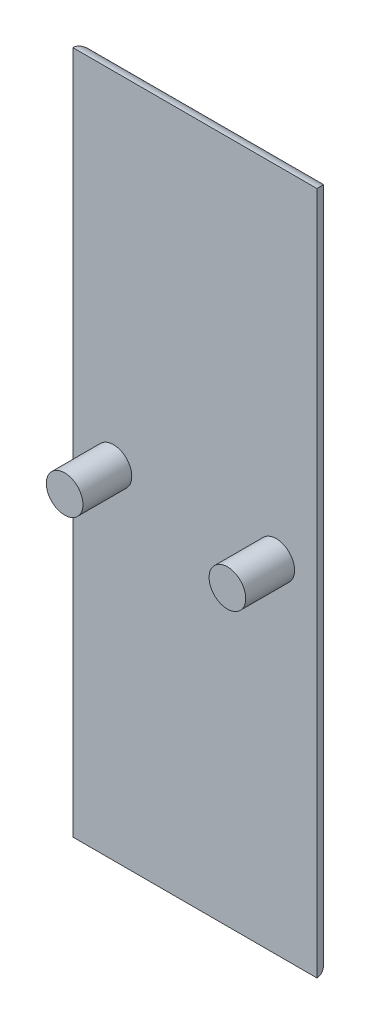
SolidWorks part; units mm, degrees
ref_plane "Front Plane" through (0, 0, 0) normal (0, 0, 1) x (1, 0, 0)
ref_plane "Top Plane" through (0, 0, 0) normal (0, 1, 0) x (1, 0, 0)
ref_plane "Right Plane" through (0, 0, 0) normal (1, 0, 0) x (0, 0, -1)
sketch "Sketch1" plane through (0, 0, 0) normal (0, 0, 1) x (1, 0, 0)
  line L1 (-15, 42) -> (15, 42)
  line L2 (-15, 42) -> (-15, -42)
  line L3 (-15, -42) -> (15, -42)
  line L4 (15, 42) -> (15, -42)
  line L5 (0, -42) -> (0, 42) construction
  line L6 (-15, 0) -> (15, 0) construction
  circle A0 centre (-10, 0) radius 2.25
  circle A1 centre (10, 0) radius 2.25
  point P0 (0, 0)
  dimension "D3" = 5
  dimension "D4" = 4.5
  dimension "D1" = 84
  dimension "D2" = 30
extrude "Boss-Extrude1" add sketch "Sketch1" along normal blind 2
extrude "Boss-Extrude2" add sketch "Sketch1<4>" along normal blind 8 contours A0 | A1 region at (-10, 0, 0) region at (10, 0, 0)
sketch "Sketch1<4>" plane through (0, 0, 0) normal (0, 0, 1) x (1, 0, 0) same geometry as "Sketch1"
fillet "Fillet1" radius 2 4 edges at (0, 42, 0) (-15, 0, 0) (0, -42, 0) (15, 0, 0)
